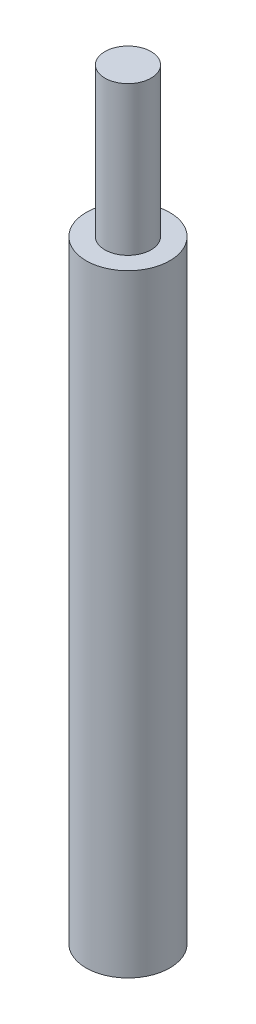
SolidWorks part; units mm, degrees
ref_plane "Front Plane" through (0, 0, 0) normal (0, 0, 1) x (1, 0, 0)
ref_plane "Top Plane" through (0, 0, 0) normal (0, 1, 0) x (1, 0, 0)
ref_plane "Right Plane" through (0, 0, 0) normal (1, 0, 0) x (0, 0, -1)
sketch "Sketch1" plane through (0, 0, 0) normal (0, 1, 0) x (1, 0, 0)
  circle A0 centre (0, 0) radius 7.1438
  dimension "D1" = 14.2875
extrude "Boss-Extrude1" add sketch "Sketch1" along normal blind 130
hole_wizard "M10x1.0 Tapped Hole1" positions "Sketch3" profile "Sketch2" tap size "M10x1.0" standard "Ansi Metric"
sketch "Sketch3" plane through (0, 0, 0) normal (0, -1, 0) x (1, 0, 0)
  point P1 (0, 0)
sketch "Sketch2" plane through (0, 0, 0) normal (1, 0, 0) x (0, 0, -1)
  line L0 (0, 0) -> (0, 17.7039)
  line L1 (0, 17.7039) -> (4.5, 15)
  line L2 (4.5, 15) -> (4.5, 0)
  line L5 (4.5, 0) -> (0, 0)
  line L10 (0, 17.7039) -> (-4.5, 15) construction
  line L11 (0, -6.35) -> (0, 107.95) construction
  dimension "Tap Drill Dia." = 9
  dimension "Tap Drill Depth" = 15
  dimension "Drill Angle" = 118
cosmetic thread "Hole Thread1" parameters "D1"=15, "D2"=10
sketch "Sketch4" plane through (0, 130, 0) normal (0, 1, 0) x (1, 0, 0)
  circle A0 centre (0, 0) radius 3.937
  circle A1 centre (0, 0) radius 7.1438
  dimension "D1" = 7.874
extrude "Cut-Extrude1" cut sketch "Sketch4" against normal blind 25.4
